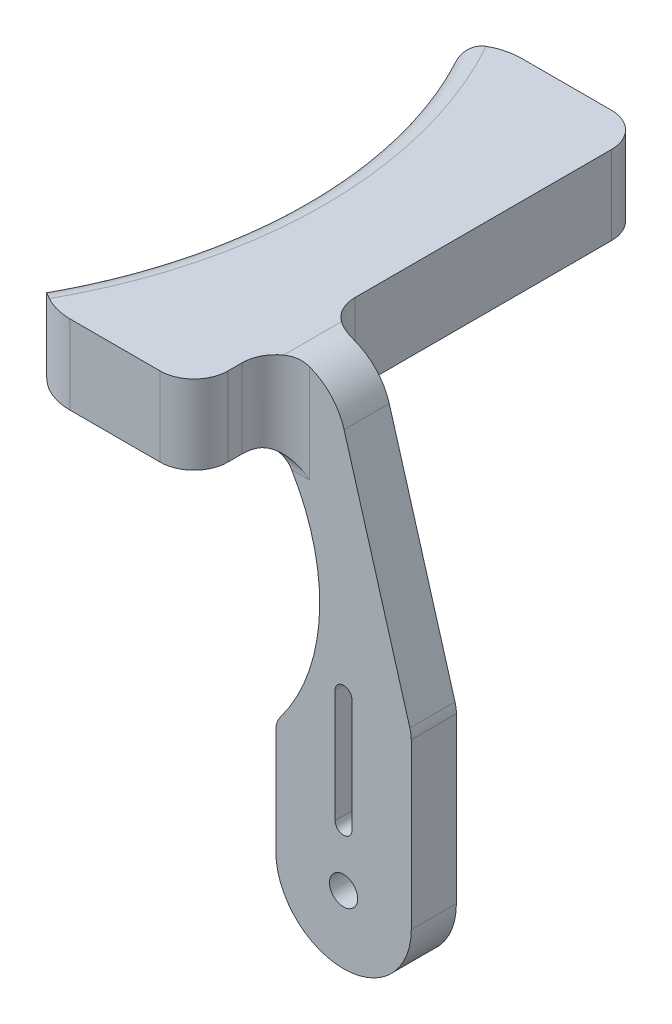
SolidWorks part; units mm, degrees
ref_plane "Alzado" through (0, 0, 0) normal (0, 0, 1) x (1, 0, 0)
ref_plane "Planta" through (0, 0, 0) normal (0, 1, 0) x (1, 0, 0)
ref_plane "Vista lateral" through (0, 0, 0) normal (1, 0, 0) x (0, 0, -1)
sketch "Croquis1" plane through (0, 0, 0) normal (0, 0, 1) x (1, 0, 0)
  line L0 (-6, 0) -> (-6, 39)
  line L1 (6, 0) -> (6, 15)
  line L3 (-6, 39) -> (-1, 39)
  line L4 (-1, 39) -> (6, 15)
  arc A0 (-6, 0) -> (6, 0) centre (0, 0) ccw
  dimension "D1" = 6
  dimension "D2" = 39
  dimension "D3" = 15
  dimension "D4" = 5
extrude "Saliente-Extruir1" add sketch "Croquis1" along normal blind 4
sketch "Croquis3" plane through (0, 39, 0) normal (0, 1, 0) x (1, 0, 0)
  line L0 (-6, -11.25) -> (-6, 28.75)
  line L1 (-6, 28.75) -> (-21, 28.75)
  line L2 (-21, 28.75) -> (-21, 26.75)
  line L3 (-21, -9.25) -> (-21, -11.25)
  line L4 (-21, -11.25) -> (-6, -11.25)
  line L6 (-6, 8.75) -> (-54.4664, 8.75) construction
  line L7 (-6, -4) -> (-6, 0) construction
  line L10 (-1, 0) -> (-6, 0) construction
  arc A0 (-21, -9.25) -> (-21, 26.75) centre (-54.4664, 8.75) ccw
  dimension "D3" = 38
  dimension "D1" = 15
  dimension "D2" = 40
  dimension "D4" = 8.75
  dimension "D5" = 2
extrude "Saliente-Extruir2" add sketch "Croquis3" against normal blind 7
fillet "Redondeo1" radius 3 5 edges at (6, 15, 2) (-6, 35.5, -28.75) (-6, 35.5, 11.25) (-6, 35.5, 4) (-6, 35.5, 0)
fillet "Redondeo2" radius 5 3 edges at (-21, 35.5, 11.25) (-21, 35.5, -28.75) (-1, 39, 2)
sketch "Croquis4" plane through (0, 0, 0) normal (0, 0, -1) x (-1, 0, 0)
  line L0 (0, 15) -> (0, 5) construction
  line L1 (0.75, 15) -> (0.75, 5)
  line L2 (-0.75, 15) -> (-0.75, 5)
  circle A0 centre (0, 0) radius 1.25
  arc A1 (0.75, 15) -> (-0.75, 15) centre (0, 15) ccw
  arc A2 (-0.75, 5) -> (0.75, 5) centre (0, 5) ccw
  point P5 (0, 10)
  dimension "D1" = 2.5
  dimension "D2" = 0.75
  dimension "D3" = 5
  dimension "D4" = 10
extrude "Cortar-Extruir1" cut sketch "Croquis4" against normal blind 10
fillet "Redondeo3" radius 2 2 edges at (-16.4664, 32, -8.75) (-16.4664, 39, -8.75)
sketch "Croquis6" plane through (0, 0, 4) normal (0, 0, 1) x (1, 0, 0)
  line L0 (-6, 32) -> (-6, 0) construction
  line L1 (-6, 0) -> (-6, 10) construction
  line L2 (-6, 10) -> (-6, 32)
  arc A0 (-6, 32) -> (-6, 10) centre (-19.6107, 21) cw
  dimension "D2" = 17.5
  dimension "D1" = 10
extrude "Cortar-Extruir2" cut sketch "Croquis6" against normal blind 10
fillet "Redondeo4" radius 2 2 edges at (-6, 10, 2) (-6, 32, 2)
fillet "Redondeo5" radius 2 2 edges at (-4.9956, 32, 0) (-4.9956, 32, 4)
